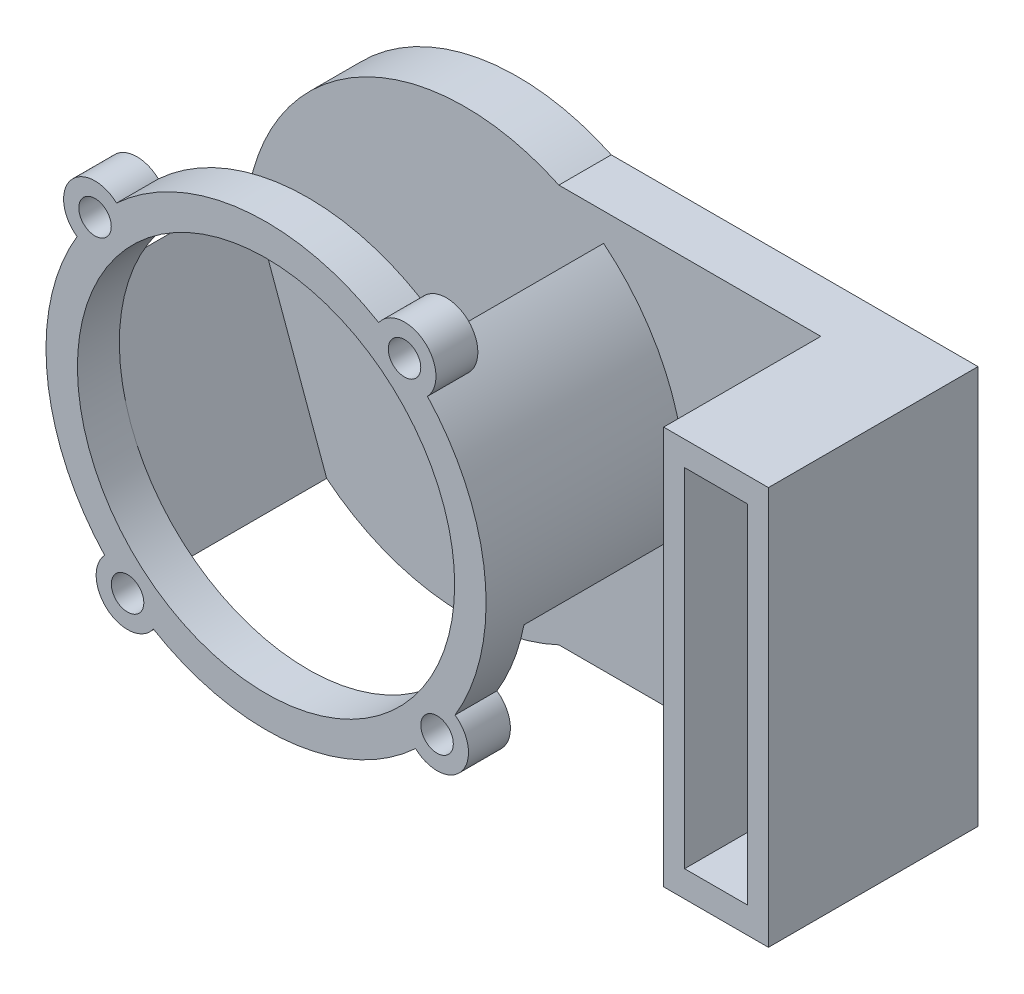
SolidWorks part; units mm, degrees
ref_plane "Piano frontale" through (0, 0, 0) normal (0, 0, 1) x (1, 0, 0)
ref_plane "Piano superiore" through (0, 0, 0) normal (0, 1, 0) x (1, 0, 0)
ref_plane "Piano destro" through (0, 0, 0) normal (1, 0, 0) x (0, 0, -1)
sketch "Schizzo1" plane through (0, 0, 0) normal (0, 0, 1) x (1, 0, 0)
  line L0 (12.3655, 11.6094) -> (47.3655, 11.6094) construction
  line L1 (12.3655, -26.3906) -> (47.3655, -26.3906)
  line L2 (47.3655, -26.3906) -> (47.3655, 11.6094)
  line L3 (47.3655, 11.6094) -> (12.3655, 11.6094)
  arc A2 (12.3655, 11.6094) -> (12.3655, -26.3906) centre (3.4212, -7.3906) ccw
  dimension "D1" = 35
  dimension "D4" = 35
  dimension "D3" = 42
  dimension "D2" = 38
extrude "Estrusione-Estrusione1" add sketch "Schizzo1" along normal mid plane 5
sketch "Schizzo2" plane through (0, 0, 2.5) normal (0, 0, 1) x (1, 0, 0)
  line L1 (37.3655, 11.6094) -> (47.3655, 11.6094)
  line L2 (37.3655, 11.6094) -> (37.3655, -26.3906)
  line L3 (37.3655, -26.3906) -> (47.3655, -26.3906)
  line L4 (47.3655, 11.6094) -> (47.3655, -26.3906)
  line L5 (37.3655, 11.6094) -> (47.3655, -26.3906) construction
  line L6 (37.3655, -26.3906) -> (47.3655, 11.6094) construction
  point P0 (42.3655, -7.3906)
  dimension "D1" = 10
extrude "Estrusione-Estrusione2" add sketch "Schizzo2" along normal blind 15
sketch "Schizzo3" plane through (0, 0, 17.5) normal (0, 0, 1) x (1, 0, 0)
  line L1 (39.3655, 9.2594) -> (45.3655, 9.2594)
  line L2 (39.3655, 9.2594) -> (39.3655, -23.8906)
  line L3 (39.3655, -23.8906) -> (45.3655, -23.8906)
  line L4 (45.3655, 9.2594) -> (45.3655, -23.8906)
  line L5 (39.3655, 9.2594) -> (45.3655, -23.8906) construction
  line L6 (39.3655, -23.8906) -> (45.3655, 9.2594) construction
  line L7 (47.3655, -26.3906) -> (47.3655, 11.6094) construction
  line L8 (37.3655, -26.3906) -> (47.3655, -26.3906) construction
  point P0 (42.3655, -7.3156)
  dimension "D1" = 6
  dimension "D2" = 2
  dimension "D3" = 33.15
  dimension "D4" = 2.5
extrude "Taglio-Estrusione1" cut sketch "Schizzo3" against normal blind 13
sketch "Schizzo5" plane through (0, 0, 2.5) normal (0, 0, 1) x (1, 0, 0)
  line L0 (37.3655, -7.3906) -> (-17.5788, -7.3906) construction
  line L1 (37.3655, 11.6094) -> (37.3655, -26.3906) construction
  line L3 (3.4212, -28.3906) -> (3.4212, 13.6094) construction
  arc A0 (12.3655, 11.6094) -> (12.3655, -26.3906) centre (3.4212, -7.3906) ccw construction
  circle A1 centre (3.4212, -7.3906) radius 21
extrude "Estrusione-Sottile1" add sketch "Schizzo5" along normal blind 19 thin thin type one direction reverse wall 3
sketch "Schizzo7" plane through (0, 0, 4.5) normal (0, 0, 1) x (1, 0, 0)
  line L0 (39.3655, -23.8906) -> (45.3655, -21.7068) construction
  line L1 (45.3655, -23.8906) -> (45.3655, 9.2594) construction
  line L2 (39.3655, -23.8906) -> (41.3406, -29.3173) construction
  line L3 (39.3655, -23.8906) -> (45.3655, -23.8906) construction
  line L4 (45.3655, -23.8906) -> (39.3655, -23.8906) construction
  dimension "D1" = 20
ref_plane "Piano1" through (-4.4069, 12.1079, 0) normal (-0.342, 0.9397, 0) x (0.9397, 0.342, 0)
sketch "Schizzo8" plane through (-4.4069, 12.1079, 0) normal (-0.342, 0.9397, 0) x (0.9397, 0.342, 0)
  line L6 (0.6872, -21.5) -> (0.6872, 2.5) construction
  line L7 (-20.3128, -21.5) -> (21.6872, -21.5) construction
  line L8 (15.5904, 2.5) -> (-20.3128, 2.5) construction
  line L9 (-17.3128, -17.5) -> (18.6872, -17.5)
  line L10 (18.6872, -17.5) -> (18.6872, -2.5)
  line L11 (2.5936, -2.5) -> (21.6872, -2.5) construction
  line L12 (18.6872, -2.5) -> (-17.3128, -2.5)
  line L13 (-17.3128, -2.5) -> (-17.3128, -17.5)
  dimension "D1" = 18
  dimension "D2" = 36
  dimension "D3" = 4
extrude "Taglio-Estrusione2" cut sketch "Schizzo8" against normal through all
sketch "Schizzo10" plane through (0, 0, 21.5) normal (0, 0, 1) x (1, 0, 0)
  line L0 (-9.7937, -23.7113) -> (16.6362, 8.93) construction
  line L2 (19.7419, -20.6056) -> (-12.8995, 5.8243) construction
  circle A0 centre (3.4212, -7.3906) radius 21 construction
  circle A2 centre (-12.8995, 5.8243) radius 3
  circle A3 centre (16.6362, 8.93) radius 3
  circle A4 centre (19.7419, -20.6056) radius 3
  circle A5 centre (-9.7937, -23.7113) radius 3
  dimension "D2" = 6
  dimension "D3" = 6
  dimension "D4" = 6
  dimension "D5" = 6
  dimension "D1" = 42
extrude "Estrusione-Estrusione3" add sketch "Schizzo10" against normal blind 4
hole_wizard "Foro per Vite M2.5-1" positions "Schizzo3D2" profile "Schizzo13" hole size "M2.5" standard "ISO"
sketch3d "Schizzo3D2"
  point P1 (16.6362, 8.93, 21.5)
  point P4 (19.7419, -20.6056, 21.5)
  point P7 (-9.7937, -23.7113, 21.5)
  point P10 (-12.8995, 5.8243, 21.5)
sketch "Schizzo13" plane through (16.6362, 8.93, 21.5) normal (1, 0, 0) x (0, -1, 0)
  line L0 (0, 0) -> (0, 3.9313)
  line L1 (0, 3.9313) -> (1.55, 3)
  line L2 (1.55, 3) -> (1.55, 0)
  line L5 (1.55, 0) -> (0, 0)
  line L10 (0, 3.9313) -> (-1.55, 3) construction
  line L11 (0, -6.35) -> (0, 107.95) construction
  dimension "Hole Dia." = 3.1
  dimension "Hole Depth" = 3
  dimension "Drill Angle" = 118
